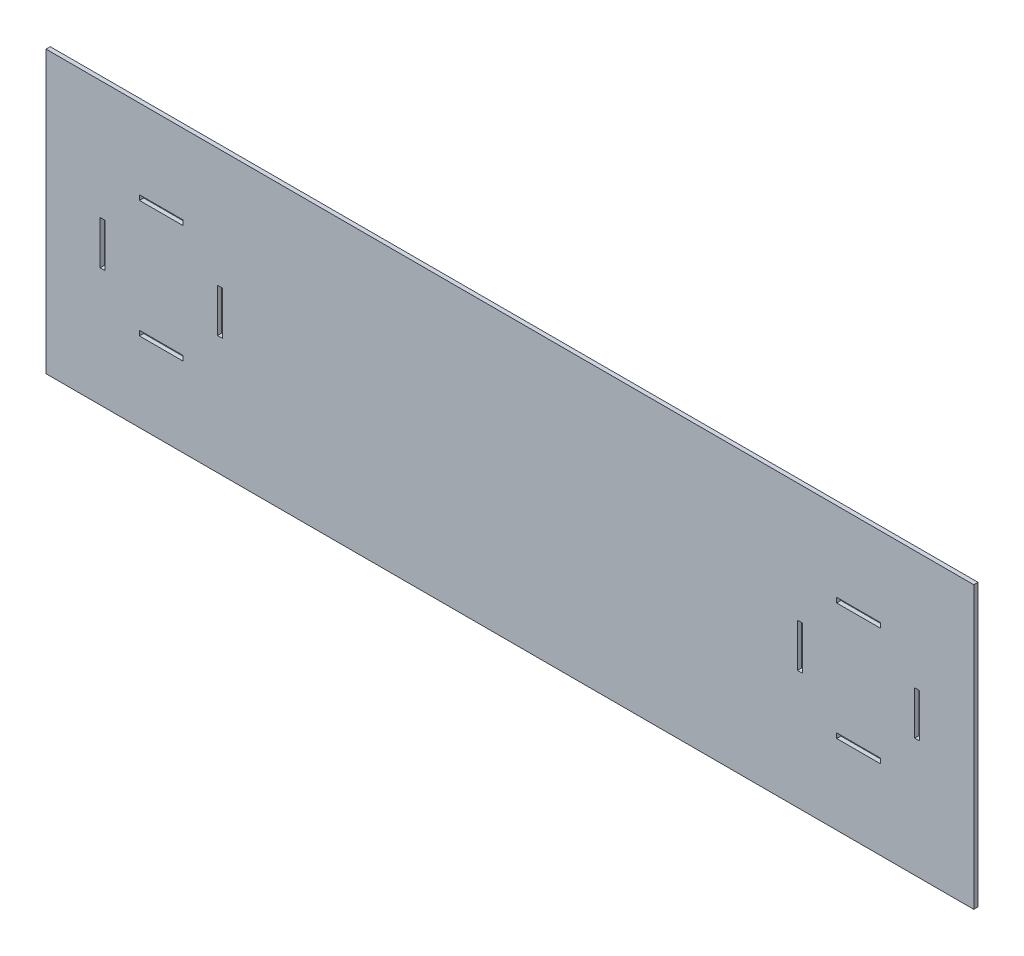
SolidWorks part; units mm, degrees
ref_plane "Plano frontal" through (0, 0, 0) normal (0, 0, 1) x (1, 0, 0)
ref_plane "Plano superior" through (0, 0, 0) normal (0, 1, 0) x (1, 0, 0)
ref_plane "Plano direito" through (0, 0, 0) normal (1, 0, 0) x (0, 0, -1)
sketch "Esboço1" plane through (0, 0, 0) normal (0, 0, 1) x (1, 0, 0)
  line L1 (-330, -100) -> (330, -100)
  line L2 (-330, -100) -> (-330, 100)
  line L3 (-330, 100) -> (330, 100)
  line L4 (330, -100) -> (330, 100)
  line L5 (-330, -100) -> (330, 100) construction
  line L6 (-330, 100) -> (330, -100) construction
  point P0 (0, 0)
  dimension "D1" = 660
  dimension "D2" = 200
extrude "Ressalto-extrusão1" add sketch "Esboço1" along normal blind 3
sketch "Esboço2" plane through (0, 0, 3) normal (0, 0, 1) x (1, 0, 0)
  line L0 (-330, 0) -> (330, 0) construction
  line L1 (-330, 100) -> (-330, -100) construction
  line L2 (330, -100) -> (330, 100) construction
  line L3 (0, 100) -> (0, -100) construction
  line L4 (330, 100) -> (-330, 100) construction
  line L5 (-330, -100) -> (330, -100) construction
  line L6 (-248, 100) -> (-248, -100) construction
  line L11 (291.5, 15.5) -> (288, 15.5)
  line L12 (288, -15.5) -> (288, 15.5)
  line L13 (-208, -15.5) -> (-204.5, -15.5)
  line L14 (-208, -15.5) -> (-208, 15.5)
  line L15 (-208, 15.5) -> (-204.5, 15.5)
  line L16 (-204.5, -15.5) -> (-204.5, 15.5)
  line L17 (-208, -15.5) -> (-204.5, 15.5) construction
  line L18 (-208, 15.5) -> (-204.5, -15.5) construction
  line L19 (-291.5, -15.5) -> (-288, -15.5)
  line L20 (-291.5, -15.5) -> (-291.5, 15.5)
  line L21 (-291.5, 15.5) -> (-288, 15.5)
  line L22 (-288, -15.5) -> (-288, 15.5)
  line L23 (-291.5, -15.5) -> (-288, 15.5) construction
  line L24 (-291.5, 15.5) -> (-288, -15.5) construction
  line L25 (-263.5, 40) -> (-232.5, 40)
  line L26 (-263.5, -43.5) -> (-232.5, -43.5)
  line L27 (-263.5, -43.5) -> (-263.5, -40)
  line L28 (-263.5, -40) -> (-232.5, -40)
  line L29 (-232.5, -43.5) -> (-232.5, -40)
  line L30 (-263.5, -43.5) -> (-232.5, -40) construction
  line L31 (-263.5, -40) -> (-232.5, -43.5) construction
  line L32 (-232.5, 43.5) -> (-232.5, 40)
  line L33 (-263.5, 43.5) -> (-232.5, 43.5)
  line L34 (-263.5, 43.5) -> (-263.5, 40)
  line L35 (291.5, -15.5) -> (288, -15.5)
  line L36 (291.5, -15.5) -> (291.5, 15.5)
  line L37 (208, 15.5) -> (204.5, 15.5)
  line L38 (204.5, -15.5) -> (204.5, 15.5)
  line L39 (208, -15.5) -> (204.5, -15.5)
  line L40 (208, -15.5) -> (208, 15.5)
  line L41 (263.5, -40) -> (232.5, -40)
  line L42 (232.5, -43.5) -> (232.5, -40)
  line L43 (263.5, -43.5) -> (232.5, -43.5)
  line L44 (263.5, -43.5) -> (263.5, -40)
  line L45 (263.5, 43.5) -> (263.5, 40)
  line L46 (263.5, 43.5) -> (232.5, 43.5)
  line L47 (232.5, 43.5) -> (232.5, 40)
  line L48 (263.5, 40) -> (232.5, 40)
  point P13 (0, 0)
  point P17 (-206.25, 0)
  point P22 (-289.75, 0)
  point P29 (-248, -41.75)
  dimension "D3" = 3.5
  dimension "D4" = 31
  dimension "D6" = 122
  dimension "D7" = 31
  dimension "D8" = 3.5
  dimension "D9" = 80
  dimension "D10" = 31
  dimension "D11" = 3.5
  dimension "D12" = 80
  dimension "D13" = 40
extrude "Corte-extrusão1" cut sketch "Esboço2" against normal through all
